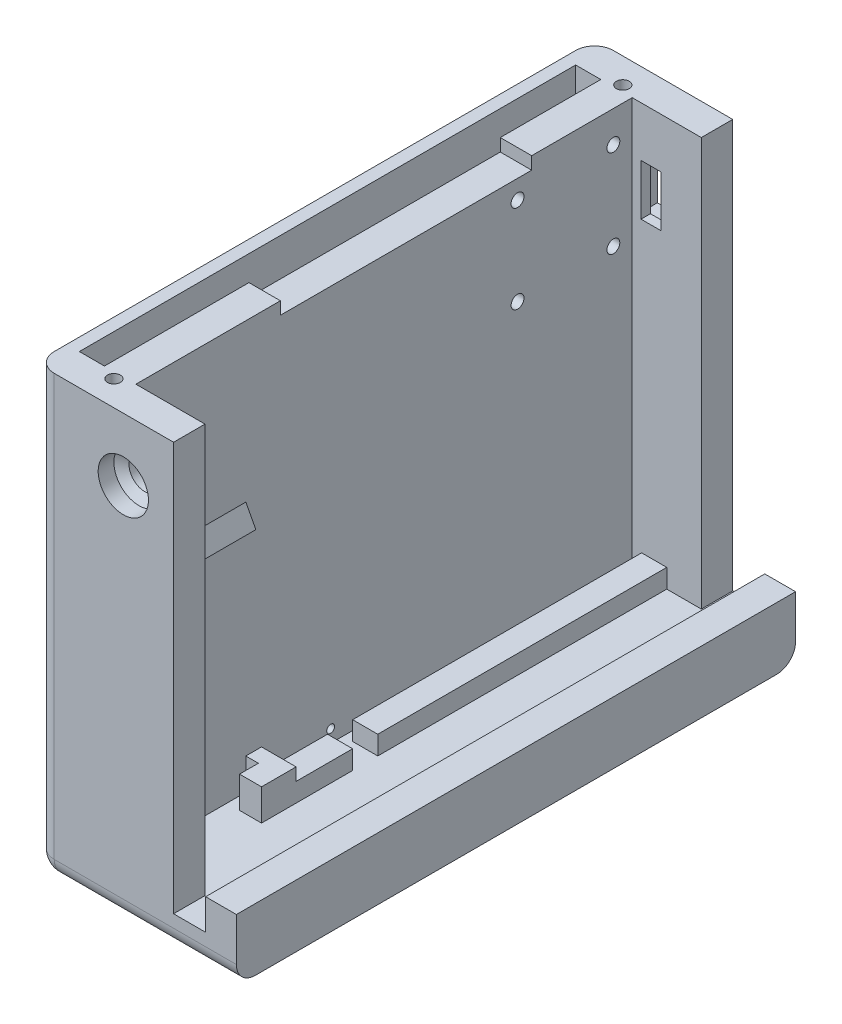
SolidWorks part; units mm, degrees
ref_plane "Front Plane" through (0, 0, 0) normal (0, 0, 1) x (1, 0, 0)
ref_plane "Top Plane" through (0, 0, 0) normal (0, 1, 0) x (1, 0, 0)
ref_plane "Right Plane" through (0, 0, 0) normal (1, 0, 0) x (0, 0, -1)
sketch "Sketch4" plane through (0, 0, 0) normal (0, 1, 0) x (1, 0, 0)
  line L0 (0, 0) -> (9, 0)
  line L1 (9, 0) -> (9, 89)
  line L2 (9, 89) -> (0, 89)
  line L3 (0, 89) -> (0, 81) construction
  line L4 (0, 81) -> (0, 8) construction
  line L5 (0, 8) -> (0, 0) construction
  line L6 (0, 81) -> (-2, 81)
  line L7 (-2, 81) -> (-2, 89)
  line L8 (-2, 89) -> (0, 89)
  line L9 (0, 8) -> (-2, 8)
  line L10 (-2, 8) -> (-2, 0)
  line L11 (-2, 0) -> (0, 0)
  line L12 (0, 8) -> (0, 5)
  line L13 (0, 5) -> (0, 0) construction
  line L14 (0, 5) -> (4, 5)
  line L15 (0, 81) -> (0, 84)
  line L16 (0, 84) -> (4, 84)
  line L17 (4, 5) -> (4, 84)
  dimension "D4" = 2
  dimension "D1" = 9
  dimension "D2" = 89
  dimension "D3" = 73
  dimension "D5" = 3
  dimension "D6" = 4
extrude "Boss-Extrude4" add sketch "Sketch4" against normal blind 65
sketch "Sketch5" plane through (-2, 0, 0) normal (-1, 0, 0) x (0, 0, 1)
  line L0 (-8, -65) -> (-8, 0) construction
  line L1 (-81, 0) -> (-8, 0)
  line L2 (-81, 0) -> (-81, -7)
  line L3 (-81, -7) -> (-8, -7)
  line L4 (-8, 0) -> (-8, -7)
  line L6 (-81, -65) -> (-8, -65)
  line L7 (-81, -65) -> (-81, -63)
  line L8 (-81, -63) -> (-8, -63)
  line L9 (-8, -65) -> (-8, -63)
  dimension "D1" = 7
  dimension "D2" = 2
extrude "Boss-Extrude5" add sketch "Sketch5" against normal up to surface (2 mm away) up to face at (0, -32.5, -82.5)
sketch "Sketch8" plane through (9, 0, 0) normal (1, 0, 0) x (0, 0, -1)
  line L0 (28, 0) -> (28, -2)
  line L1 (0, 0) -> (89, 0) construction
  line L2 (28, -2) -> (68, -2)
  line L3 (68, -2) -> (68, 0)
  line L4 (89, -65) -> (89, 0) construction
  line L5 (84, 0) -> (5, 0) construction
  dimension "D1" = 2
  dimension "D2" = 40
  dimension "D3" = 21
extrude "Cut-Extrude8" cut sketch "Sketch8" against normal blind 5 and the other way through all
sketch "Sketch9" plane through (9, 0, 0) normal (1, 0, 0) x (0, 0, -1)
  line L0 (89, -65) -> (89, -62)
  line L1 (89, -62) -> (84, -62)
  line L2 (84, -62) -> (84, -65)
  line L4 (25, -65) -> (25, -62)
  line L5 (25, -62) -> (22.5, -62)
  line L8 (0, -65) -> (89, -65) construction
  line L9 (89, -65) -> (89, 0) construction
  line L11 (22.5, -62) -> (22.5, -65)
  line L13 (22.5, -65) -> (25, -65)
  line L15 (84, -65) -> (89, -65)
  dimension "D1" = 59
  dimension "D2" = 3
  dimension "D3" = 2.5
  dimension "D4" = 5
extrude "Boss-Extrude8" add sketch "Sketch9" along normal blind 1.5
sketch "Sketch10" plane through (10.5, 0, 0) normal (1, 0, 0) x (0, 0, -1)
  line L5 (22.5, -65) -> (89, -65)
  line L6 (22.5, -65) -> (22.5, -62)
  line L7 (22.5, -62) -> (89, -62)
  line L8 (89, -65) -> (89, -62)
extrude "Boss-Extrude9" add sketch "Sketch10" along normal blind 4
hole_wizard "M2.5x0.45 Tapped Hole1" positions "Sketch15" profile "Sketch16" tap size "M2.5x0.45" standard "ANSI Metric"
sketch "Sketch15" plane through (9, 0, 0) normal (1, 0, 0) x (0, 0, -1)
  line L0 (89, -62) -> (89, 0) construction
  line L3 (68, 0) -> (89, 0) construction
  point P0 (81, -5)
  point P4 (65.75, -19)
  point P6 (81, -19)
  point P30 (65.75, -5)
  dimension "D1" = 15.25
  dimension "D2" = 14
  dimension "D3" = 8
  dimension "D4" = 5
sketch "Sketch16" plane through (9, -5, -81) normal (0, 1, 0) x (0, 0, -1)
  line L0 (0, 0) -> (0, 4)
  line L1 (0, 4) -> (1.025, 3.3841)
  line L2 (1.025, 3.3841) -> (1.025, 0)
  line L5 (1.025, 0) -> (0, 0)
  line L10 (0, 4) -> (-1.025, 3.3841) construction
  line L11 (0, -6.35) -> (0, 107.95) construction
  dimension "Tap Drill Dia." = 2.05
  dimension "Tap Drill Depth" = 4
  dimension "Drill Angle" = 118
cosmetic thread "Hole Thread2" parameters "D1"=3.38, "D2"=2.5
cosmetic thread "Hole Thread3" parameters "D1"=3.38, "D2"=2.5
cosmetic thread "Hole Thread5" parameters "D1"=3.38, "D2"=2.5
cosmetic thread "Hole Thread8" parameters "D1"=3.38, "D2"=2.5
sketch "Sketch17" plane through (0, 0, 0) normal (0, 1, 0) x (1, 0, 0)
  line L1 (9, 89) -> (20, 89)
  line L2 (9, 89) -> (9, 84)
  line L4 (9, 84) -> (20, 84)
  line L5 (9, 0) -> (20, 0)
  line L6 (9, 0) -> (9, 5)
  line L7 (9, 5) -> (20, 5)
  line L8 (20, 0) -> (20, 5)
  line L9 (20, 89) -> (20, 84)
  dimension "D1" = 5
  dimension "D2" = 11
extrude "Boss-Extrude20" add sketch "Sketch17" against normal up to surface (65 mm away) up to face at (7.1667, -65, -37.1667)
sketch "Sketch18" plane through (0, 0, -84) normal (0, 0, 1) x (1, 0, 0)
  line L5 (8, -17.5) -> (16, -17.5)
  line L6 (8, -17.5) -> (8, -6.5)
  line L7 (8, -6.5) -> (16, -6.5)
  line L8 (16, -17.5) -> (16, -6.5)
  line L9 (8, -17.5) -> (16, -6.5) construction
  line L10 (8, -6.5) -> (16, -17.5) construction
  line L11 (9, -65) -> (9, 0) construction
  line L13 (9, 0) -> (20, 0) construction
  point P0 (12, -12)
  dimension "D1" = 11
  dimension "D2" = 8
  dimension "D3" = 3
  dimension "D4" = 12
extrude "Cut-Extrude10" cut sketch "Sketch18" against normal up to next
sketch "Sketch20" plane through (9, 0, 0) normal (1, 0, 0) x (0, 0, -1)
  line L9 (25, -62) -> (22.5, -62)
  line L10 (25, -62) -> (25, -60)
  line L11 (25, -60) -> (22.5, -60)
  line L13 (22.5, -60) -> (22.5, -62)
  dimension "D1" = 2
extrude "Boss-Extrude13" add sketch "Sketch20" along normal up to surface (5.5 mm away) up to face at (14.5, -63.5, -53.25)
sketch "Sketch22" plane through (0, 0, -22.5) normal (0, 0, 1) x (1, 0, 0)
  line L2 (14.5, -60) -> (14.5, -65)
  line L6 (14.5, -60) -> (14.5, -65) construction
  line L7 (14.5, -65) -> (9, -65) construction
  line L8 (14.5, -60) -> (11, -60)
  line L9 (14.5, -60) -> (14.5, -65)
  line L10 (14.5, -65) -> (11, -65)
  line L11 (11, -60) -> (11, -65)
  line L12 (9, -60) -> (9, -65) construction
  line L13 (14.5, -60) -> (9, -60) construction
  line M8 (14.5, -60) -> (9, -60)
  line M15 (9, -65) -> (14.5, -65)
  line M16 (14.5, -65) -> (14.5, -60)
  dimension "D1" = 2
extrude "Boss-Extrude21" add sketch "Sketch22" along normal blind 3 contours L11 M8 M15 M16 region at (12.75, -62.5, -22.5)
sketch "Sketch23" plane through (0, 0, -5) normal (0, 0, -1) x (-1, 0, 0)
  line L3 (-11, -60) -> (-14.4996, -60)
  line L4 (-14.4996, -65) -> (-14.4996, -60)
  line L8 (-9, -65) -> (-20, -65) construction
  line L9 (-14.4996, -65) -> (-11, -65)
  line L10 (-11, -65) -> (-11, -60)
  line L11 (-9, -65) -> (-9, 0) construction
  dimension "D1" = 2
  dimension "D2" = 5
  dimension "D3" = 3.4996
extrude "Boss-Extrude17" add sketch "Sketch23" along normal blind 3
sketch "Sketch24" plane through (0, 0, -5) normal (0, 0, -1) x (-1, 0, 0)
  line L0 (-9, -25) -> (-10.6, -28)
  line L2 (-10.6, -28) -> (-9, -28)
  line L3 (-9, -28) -> (-9, -25)
  line L4 (-9, -65) -> (-9, 0) construction
  dimension "D1" = 1.6
  dimension "D2" = 3
  dimension "D3" = 37
extrude "Boss-Extrude18" add sketch "Sketch24" along normal up to vertex (17.5 mm away) up to point (9, -60, -22.5)
hole_wizard "M1.6x0.35 Tapped Hole2" positions "3DSketch2" profile "Sketch25" tap size "M1.6x0.35" standard "ANSI Metric"
sketch3d "3DSketch2"
  line L2 (9, -65, -25) -> (9, -60, -25) construction
  line L3 (9, -65, -25) -> (9, -65, -84) construction
  point P0 (9, -63, -36)
  dimension "D1" = 2
  dimension "D2" = 11
sketch "Sketch25" plane through (9, -63, -36) normal (0, 1, 0) x (0, 0, -1)
  line L0 (0, 0) -> (0, 4.3755)
  line L1 (0, 4.3755) -> (0.625, 4)
  line L2 (0.625, 4) -> (0.625, 0)
  line L5 (0.625, 0) -> (0, 0)
  line L10 (0, 4.3755) -> (-0.625, 4) construction
  line L11 (0, -6.35) -> (0, 107.95) construction
  dimension "Tap Drill Dia." = 1.25
  dimension "Tap Drill Depth" = 4
  dimension "Drill Angle" = 118
cosmetic thread "Hole Thread6" parameters "D1"=3.2, "D2"=1.6
sketch "Sketch27" plane through (14.5, 0, 0) normal (1, 0, 0) x (0, 0, -1)
  line L0 (84, -62) -> (25, -62) construction
  line L1 (34, -62) -> (38, -62)
  line L2 (34, -62) -> (34, -65)
  line L3 (34, -65) -> (38, -65)
  line L4 (38, -62) -> (38, -65)
  line L5 (19.5, -65) -> (84, -65) construction
  line L6 (25, -60) -> (25, -62) construction
  dimension "D1" = 4
  dimension "D2" = 9
extrude "Cut-Extrude12" cut sketch "Sketch27" against normal up to surface (5.5 mm away) up to face at (9, -63, -36.625)
hole_wizard "M2.5x0.45 Tapped Hole2" positions "3DSketch4" profile "Sketch28" tap size "M2.5x0.45" standard "ANSI Metric"
sketch3d "3DSketch4"
  line L24 (-2, -32.5, -89) -> (20, -32.5, -89) construction
  line L25 (-2, -65, -89) -> (-2, 0, -89) construction
  line L26 (20, -65, -89) -> (20, 0, -89) construction
  line L27 (-2, 0, 0) -> (20, 0, 0) construction
  line L29 (20, 0, -89) -> (-2, 0, -89) construction
  line L30 (4, 0, -5) -> (9, 0, -5) construction
  line L31 (4, 0, -28) -> (4, 0, -5) construction
  line L32 (9, 0, -5) -> (9, 0, -28) construction
  line L34 (6.5, 0, -5) -> (6.5, 0, 0) construction
  line L36 (6.5, 0, -5) -> (6.5, 0, -89) construction
  point P0 (6.5, 0, -4)
  point P2 (6.5, 0, -85)
  dimension "D1" = 4
  dimension "D3" = 4
sketch "Sketch28" plane through (6.5, 0, -4) normal (1, 0, 0) x (0, 0, 1)
  line L0 (0, 0) -> (0, 4.6159)
  line L1 (0, 4.6159) -> (1.025, 4)
  line L2 (1.025, 4) -> (1.025, 0)
  line L5 (1.025, 0) -> (0, 0)
  line L10 (0, 4.6159) -> (-1.025, 4) construction
  line L11 (0, -6.35) -> (0, 107.95) construction
  dimension "Tap Drill Dia." = 2.05
  dimension "Tap Drill Depth" = 4
  dimension "Drill Angle" = 118
cosmetic thread "Hole Thread11" parameters "D1"=5, "D2"=2.5
cosmetic thread "Hole Thread12" parameters "D1"=5, "D2"=2.5
sketch "Sketch31" plane through (0, 0, -84) normal (0, 0, -1) x (-1, 0, 0)
  line L1 (-13.6, -7.95) -> (-10.4, -7.95)
  line L2 (-13.6, -7.95) -> (-13.6, -16.05)
  line L3 (-13.6, -16.05) -> (-10.4, -16.05)
  line L4 (-10.4, -7.95) -> (-10.4, -16.05)
  line L5 (-13.6, -7.95) -> (-10.4, -16.05) construction
  line L6 (-13.6, -16.05) -> (-10.4, -7.95) construction
  line L8 (-9, -6.5) -> (-9, -17.5) construction
  line L9 (-8, -6.5) -> (-16, -6.5)
  line L10 (-8, -6.5) -> (-8, -17.5)
  line L11 (-8, -17.5) -> (-16, -17.5)
  line L12 (-16, -6.5) -> (-16, -17.5)
  point P0 (-12, -12)
  dimension "D1" = 8.1
  dimension "D2" = 3.2
  dimension "D3" = 1.4
  dimension "D4" = 1.45
extrude "Boss-Extrude22" add sketch "Sketch31" along normal blind 1.5
hole_wizard "Ø5.0mm Dowel Hole1" positions "Sketch32" profile "Sketch33" hole size "Ø5.0" standard "ANSI Metric" end condition through all
sketch "Sketch32" plane through (0, 0, -5) normal (0, 0, -1) x (-1, 0, 0)
  line L6 (-20, 0) -> (-9, 0) construction
  line L7 (-20, -65) -> (-20, 0) construction
  point P0 (-12, -10)
  dimension "D1" = 10
  dimension "D2" = 8
sketch "Sketch33" plane through (12, -10, -5) normal (1, 0, 0) x (0, 1, 0)
  line L0 (0, 0) -> (0, 5)
  line L1 (0, 5) -> (2.5, 5)
  line L2 (2.5, 5) -> (2.5, 0)
  line L5 (2.5, 0) -> (0, 0)
  line L11 (0, -6.35) -> (0, 107.95) construction
  dimension "Thru Hole Dia." = 5
  dimension "Thru Hole Depth" = 5
sketch "Sketch36" plane through (0, -65, 0) normal (0, -1, 0) x (1, 0, 0)
  line L1 (-2, 0) -> (20, 0)
  line L2 (-2, 0) -> (-2, -89)
  line L3 (-2, -89) -> (20, -89)
  line L4 (20, 0) -> (20, -89)
extrude "Boss-Extrude23" add sketch "Sketch36" along normal blind 5
hole_wizard "Ø8.0mm Dowel Hole1" positions "Sketch39" profile "Sketch40" hole size "Ø8.0" standard "ANSI Metric"
sketch "Sketch39" plane through (0, 0, 0) normal (0, 0, 1) x (1, 0, 0)
  point P0 (12, -10)
sketch "Sketch40" plane through (12, -10, 0) normal (1, 0, 0) x (0, -1, 0)
  line L0 (0, 0) -> (0, 4.9034)
  line L1 (0, 4.9034) -> (4, 2.5)
  line L2 (4, 2.5) -> (4, 0)
  line L5 (4, 0) -> (0, 0)
  line L10 (0, 4.9034) -> (-4, 2.5) construction
  line L11 (0, -6.35) -> (0, 107.95) construction
  dimension "Hole Dia." = 8
  dimension "Hole Depth" = 2.5
  dimension "Drill Angle" = 118
sketch "Sketch42" plane through (0, -7, 0) normal (0, -1, 0) x (1, 0, 0)
  line L1 (-2, -8) -> (0, -8)
  line L2 (-2, -8) -> (-2, -81)
  line L3 (-2, -81) -> (0, -81)
  line L4 (0, -8) -> (0, -81)
extrude "Boss-Extrude25" add sketch "Sketch42" along normal blind 1.5
sketch "Sketch43" plane through (0, -63, 0) normal (0, 1, 0) x (1, 0, 0)
  line L1 (-2, 81) -> (0, 81)
  line L2 (-2, 81) -> (-2, 8)
  line L3 (-2, 8) -> (0, 8)
  line L4 (0, 81) -> (0, 8)
extrude "Cut-Extrude13" cut sketch "Sketch43" against normal blind 1.5
sketch "Sketch44" plane through (0, -65, 0) normal (0, 1, 0) x (1, 0, 0)
  line L1 (4, 84) -> (0, 84)
  line L2 (4, 84) -> (4, 5)
  line L3 (4, 5) -> (0, 5)
  line L4 (0, 84) -> (0, 5)
extrude "Cut-Extrude14" cut sketch "Sketch44" against normal blind 1.5
sketch "Sketch46" plane through (0, -70, 0) normal (0, -1, 0) x (1, 0, 0)
  line L0 (25, 0) -> (25, -89)
  line L1 (20, 0) -> (30, 0)
  line L2 (20, 0) -> (20, -89)
  line L3 (20, -89) -> (30, -89)
  line L4 (30, 0) -> (30, -89)
  line M8 (20, -89) -> (20, 0)
  dimension "D1" = 10
extrude "Boss-Extrude26" add sketch "Sketch46" against normal blind 10 separate body contours L4 L1 L0 L3 region at (27.5, -70, -44.5)
extrude "Boss-Extrude27" add sketch "Sketch46<3>" against normal up to surface (5 mm away) contours L3 L0 L1 M8 region at (22.5, -70, -44.5) up to face at (12.45, -65, -32.5)
sketch "Sketch46<3>" plane through (0, -70, 0) normal (0, -1, 0) x (1, 0, 0) same geometry as "Sketch46"
fillet "Fillet1" radius 3 5 edges at (-2, -70, -44.5) (14, -70, 0) (-2, -35, 0) (-2, -35, -89) (14, -70, -89)
sketch "Sketch47" plane through (0, -60, 0) normal (0, 1, 0) x (1, 0, 0)
  line L1 (25, 89) -> (30, 89)
  line L2 (25, 89) -> (25, 0)
  line L3 (25, 0) -> (30, 0)
  line L4 (30, 89) -> (30, 0)
extrude "Cut-Extrude15" cut sketch "Sketch47" against normal blind 0.1
sketch "Sketch48" plane through (25, 0, 0) normal (-1, 0, 0) x (0, 0, 1)
  line L1 (-89, -60.1) -> (0, -60.1)
  line L2 (-89, -60.1) -> (-89, -65)
  line L3 (-89, -65) -> (0, -65)
  line L4 (0, -60.1) -> (0, -65)
extrude "Cut-Extrude16" cut sketch "Sketch48" against normal blind 0.1
